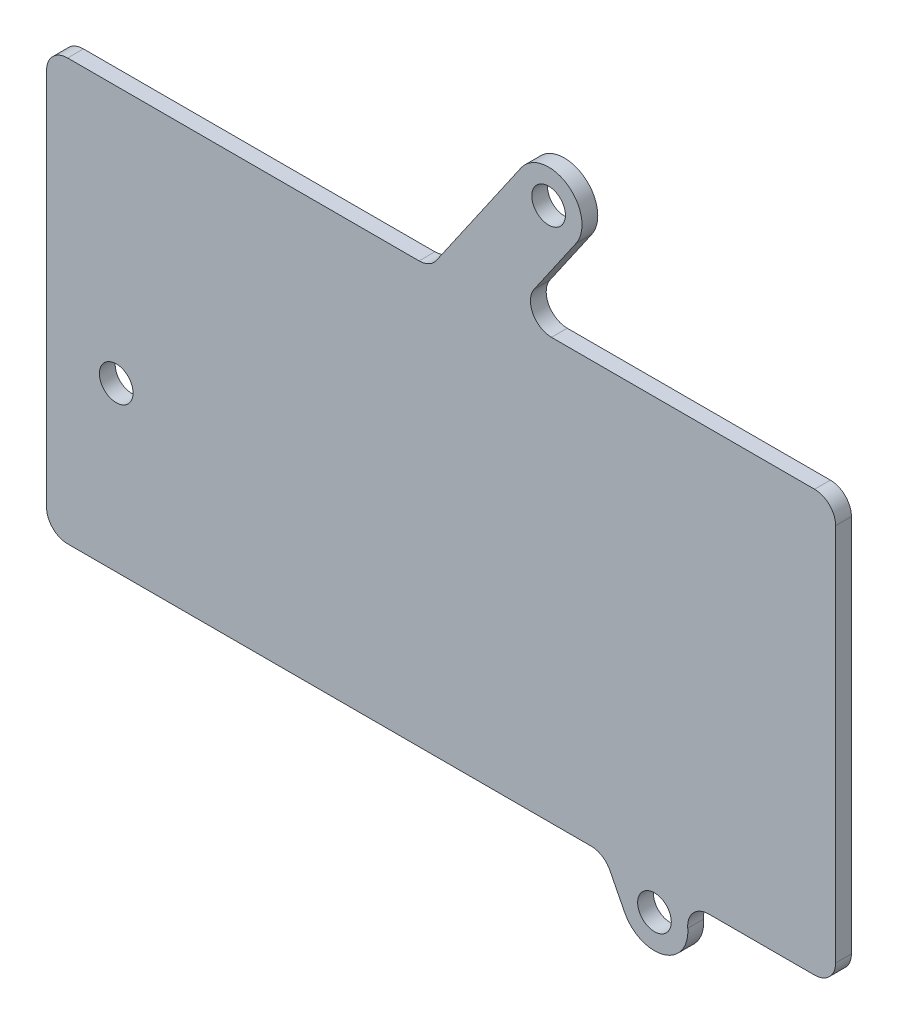
SolidWorks part; units mm, degrees
ref_plane "Front" through (0, 0, 0) normal (0, 0, 1) x (1, 0, 0)
ref_plane "Top" through (0, 0, 0) normal (0, 1, 0) x (1, 0, 0)
ref_plane "Right" through (0, 0, 0) normal (1, 0, 0) x (0, 0, -1)
sketch "Sketch1" plane through (0, 0, 19) normal (0, 0, 1) x (1, 0, 0)
  line L20 (3.8756, 32.2497) -> (-65.2244, 32.2497)
  line L21 (-65.2244, 32.2497) -> (-65.2244, -1.8503)
  line L22 (-65.2244, -1.8503) -> (3.8756, -1.8503)
  line L23 (3.8756, -1.8503) -> (3.8756, 32.2497)
  line L24 (4.8756, -2.3003) -> (4.8756, 32.6997)
  line L25 (-65.6744, -2.8503) -> (4.3256, -2.8503)
  line L26 (-66.2244, 32.6997) -> (-66.2244, -2.3003)
  line L27 (4.3256, 33.2497) -> (-65.6744, 33.2497)
  line L28 (4.8756, -2.3003) -> (4.8756, 32.6997)
  line L29 (-65.6744, -2.8503) -> (4.3256, -2.8503)
  line L30 (-66.2244, 32.6997) -> (-66.2244, -2.3003)
  line L31 (4.3256, 33.2497) -> (-65.6744, 33.2497)
  arc A16 (3.8756, 32.2497) -> (3.8756, 32.2497) centre (3.8756, 32.2497) ccw
  arc A17 (-65.2244, 32.2497) -> (-65.2244, 32.2497) centre (-65.2244, 32.2497) ccw
  arc A18 (-65.2244, -1.8503) -> (-65.2244, -1.8503) centre (-65.2244, -1.8503) ccw
  arc A19 (3.8756, -1.8503) -> (3.8756, -1.8503) centre (3.8756, -1.8503) ccw
  arc A20 (4.8756, 32.6997) -> (4.3256, 33.2497) centre (4.3256, 32.6997) ccw
  arc A21 (4.3256, -2.8503) -> (4.8756, -2.3003) centre (4.3256, -2.3003) ccw
  arc A22 (-66.2244, -2.3003) -> (-65.6744, -2.8503) centre (-65.6744, -2.3003) ccw
  arc A23 (-65.6744, 33.2497) -> (-66.2244, 32.6997) centre (-65.6744, 32.6997) ccw
  arc A24 (4.8756, 32.6997) -> (4.3256, 33.2497) centre (4.3256, 32.6997) ccw
  arc A25 (4.3256, -2.8503) -> (4.8756, -2.3003) centre (4.3256, -2.3003) ccw
  arc A26 (-66.2244, -2.3003) -> (-65.6744, -2.8503) centre (-65.6744, -2.3003) ccw
  arc A27 (-65.6744, 33.2497) -> (-66.2244, 32.6997) centre (-65.6744, 32.6997) ccw
  dimension "D1" = 0.45
  dimension "D2" = 1
extrude "Boss-Extrude1" add sketch "Sketch1" against normal blind 1.5 contours L31 A27 L30 A26 L29 A25 L28 A24 L23 L22 L21 L20 region at (4.1506, -2.1254, 19)
sketch "Sketch2" plane through (0, 0, 19) normal (0, 0, 1) x (1, 0, 0)
  line L4 (6.8256, -2.8003) -> (6.8256, 33.1997)
  line L5 (4.8256, 35.1997) -> (-66.1744, 35.1997)
  line L6 (-68.1744, 33.1997) -> (-68.1744, -2.8003)
  line L7 (-66.1744, -4.8003) -> (4.8256, -4.8003)
  line L8 (6.8256, -2.8003) -> (6.8256, 33.1997)
  line L9 (4.8256, 35.1997) -> (-66.1744, 35.1997)
  line L10 (-68.1744, 33.1997) -> (-68.1744, -2.8003)
  line L11 (-66.1744, -4.8003) -> (4.8256, -4.8003)
  arc A4 (6.8256, 33.1997) -> (4.8256, 35.1997) centre (4.8256, 33.1997) ccw
  arc A5 (-66.1744, 35.1997) -> (-68.1744, 33.1997) centre (-66.1744, 33.1997) ccw
  arc A6 (-68.1744, -2.8003) -> (-66.1744, -4.8003) centre (-66.1744, -2.8003) ccw
  arc A7 (4.8256, -4.8003) -> (6.8256, -2.8003) centre (4.8256, -2.8003) ccw
  arc A8 (6.8256, 33.1997) -> (4.8256, 35.1997) centre (4.8256, 33.1997) ccw
  arc A9 (-66.1744, 35.1997) -> (-68.1744, 33.1997) centre (-66.1744, 33.1997) ccw
  arc A10 (-68.1744, -2.8003) -> (-66.1744, -4.8003) centre (-66.1744, -2.8003) ccw
  arc A11 (4.8256, -4.8003) -> (6.8256, -2.8003) centre (4.8256, -2.8003) ccw
  dimension "D1" = 0
extrude "Boss-Extrude2" add sketch "Sketch2" along normal blind 1.5
sketch "Sketch3" plane through (0, 0, 20.5) normal (0, 0, 1) x (1, 0, 0)
  line L0 (-14.6371, -5.8935) -> (-13.2245, -8.6704) construction
  line L1 (-14.6371, -5.8935) -> (-13.2245, -8.6704)
  line L2 (-16.4197, -4.8003) -> (-5.2376, -4.8003)
  line L3 (-23.0706, 47.7112) -> (-31.122, 36.0625) construction
  line L4 (-21.8308, 38.3368) -> (-17.847, 44.1006) construction
  line L5 (-23.0706, 47.7112) -> (-31.122, 36.0625)
  line L6 (-21.8308, 38.3368) -> (-17.847, 44.1006)
  line L7 (-20.1856, 35.1997) -> (-32.7673, 35.1997)
  arc A0 (-5.2376, -4.8003) -> (-6.2058, -5.0503) centre (-5.2376, -6.8003) ccw construction
  arc A1 (-6.2058, -5.0503) -> (-7.2306, -6.9667) centre (-5.2376, -6.8003) ccw construction
  arc A2 (-13.2245, -8.6704) -> (-7.2306, -6.9667) centre (-10.3946, -7.2308) ccw construction
  arc A3 (-14.6371, -5.8935) -> (-15.4514, -5.0503) centre (-16.4197, -6.8003) ccw construction
  arc A4 (-15.4514, -5.0503) -> (-16.4197, -4.8003) centre (-16.4197, -6.8003) ccw construction
  arc A5 (-5.2376, -4.8003) -> (-6.2058, -5.0503) centre (-5.2376, -6.8003) ccw
  arc A6 (-6.2058, -5.0503) -> (-7.2306, -6.9667) centre (-5.2376, -6.8003) ccw
  arc A7 (-13.2245, -8.6704) -> (-7.2306, -6.9667) centre (-10.3946, -7.2308) ccw
  arc A8 (-14.6371, -5.8935) -> (-15.4514, -5.0503) centre (-16.4197, -6.8003) ccw
  arc A9 (-15.4514, -5.0503) -> (-16.4197, -4.8003) centre (-16.4197, -6.8003) ccw
  circle A10 centre (-10.3946, -7.2308) radius 1.6 construction
  circle A11 centre (-10.3946, -7.2308) radius 1.6
  circle A12 centre (-61.5567, 10.7309) radius 1.6 construction
  circle A13 centre (-61.5567, 10.7309) radius 1.6
  arc A14 (-32.7673, 35.1997) -> (-31.799, 35.4497) centre (-32.7673, 37.1997) ccw construction
  arc A15 (-31.799, 35.4497) -> (-31.122, 36.0625) centre (-32.7673, 37.1997) ccw construction
  arc A16 (-17.847, 44.1006) -> (-23.0706, 47.7112) centre (-20.4588, 45.9059) ccw construction
  arc A17 (-21.8308, 38.3368) -> (-21.1538, 35.4497) centre (-20.1856, 37.1997) ccw construction
  arc A18 (-21.1538, 35.4497) -> (-20.1856, 35.1997) centre (-20.1856, 37.1997) ccw construction
  arc A19 (-32.7673, 35.1997) -> (-31.799, 35.4497) centre (-32.7673, 37.1997) ccw
  arc A20 (-31.799, 35.4497) -> (-31.122, 36.0625) centre (-32.7673, 37.1997) ccw
  arc A21 (-17.847, 44.1006) -> (-23.0706, 47.7112) centre (-20.4588, 45.9059) ccw
  arc A22 (-21.8308, 38.3368) -> (-21.1538, 35.4497) centre (-20.1856, 37.1997) ccw
  arc A23 (-21.1538, 35.4497) -> (-20.1856, 35.1997) centre (-20.1856, 37.1997) ccw
  circle A24 centre (-20.4588, 45.9059) radius 1.6 construction
  circle A25 centre (-20.4588, 45.9059) radius 1.6
extrude "Boss-Extrude3" add sketch "Sketch3" against normal up to surface (1.5 mm away) up to face at (-30.6744, 15.1997, 19)
extrude "Cut-Extrude1" cut sketch "Sketch3<2>" against normal through all contours A13 region at (-61.5567, 10.7309, 20.5)
sketch "Sketch3<2>" plane through (0, 0, 20.5) normal (0, 0, 1) x (1, 0, 0) same geometry as "Sketch3"
